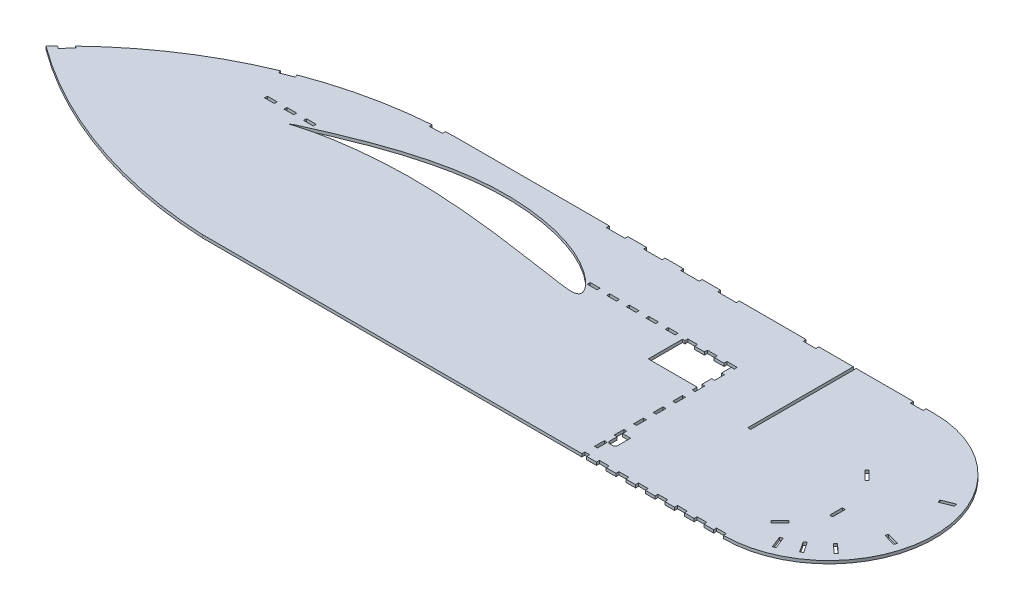
SolidWorks part; units mm, degrees
ref_plane "Front Plane" through (0, 0, 0) normal (0, 0, 1) x (1, 0, 0)
ref_plane "Top Plane" through (0, 0, 0) normal (0, 1, 0) x (1, 0, 0)
ref_plane "Right Plane" through (0, 0, 0) normal (1, 0, 0) x (0, 0, -1)
sketch "Sketch1" plane through (0, 0, 0) normal (0, 1, 0) x (1, 0, 0)
  line L0 (800, 108) -> (0, 108) construction
  line L1 (266.4083, 0) -> (800, 0)
  line L2 (0, 0) -> (0, 216) construction
  line L3 (316.2946, 216) -> (800, 216)
  arc A0 (800, 216) -> (800, 0) centre (800, 108) cw
  arc A2 (266.4083, 0) -> (19.4291, 86.8932) centre (286.1808, 450.645) cw
  arc A4 (19.4291, 86.8932) -> (316.2946, 216) centre (316.2946, -189.8565) cw
  dimension "D1" = 800
  dimension "D2" = 216
extrude "Boss-Extrude1" add sketch "Sketch1" along normal blind 3
sketch "Sketch2" plane through (0, 0, 0) normal (0, -1, 0) x (1, 0, 0)
  line L0 (605.07, -153) -> (605.07, 81) construction
  line L1 (647.57, -153) -> (637.57, -153)
  line L2 (655.07, -153) -> (655.07, -143)
  line L3 (655.07, -118) -> (605.07, -118)
  line L4 (823.6893, -121.2328) -> (814.4969, -130.4252)
  line L5 (814.4969, -130.4252) -> (816.6182, -132.5465)
  line L6 (816.6182, -132.5465) -> (825.8106, -123.3541)
  line L7 (825.8106, -123.3541) -> (823.6893, -121.2328)
  line L8 (823.6893, -121.2328) -> (814.4969, -130.4252)
  line L9 (814.4969, -130.4252) -> (816.6182, -132.5465)
  line L10 (816.6182, -132.5465) -> (825.8106, -123.3541)
  line L11 (825.8106, -123.3541) -> (823.6893, -121.2328)
  line L12 (605.07, -153) -> (605.07, -118)
  line L13 (778.5, -216) -> (791.5, -216) construction
  line L14 (791.5, -216) -> (791.5, -213) construction
  line L15 (791.5, -213) -> (778.5, -213) construction
  line L16 (778.5, -213) -> (778.5, -216) construction
  line L17 (668.6076, -216) -> (681.6076, -216) construction
  line L18 (681.6076, -216) -> (681.6076, -213) construction
  line L19 (681.6076, -213) -> (668.6076, -213) construction
  line L20 (833.1606, -28.1059) -> (837.9352, -16.0144)
  line L21 (837.9352, -16.0144) -> (835.1449, -14.9126)
  line L22 (835.1449, -14.9126) -> (830.3703, -27.0041)
  line L23 (830.3703, -27.0041) -> (833.1606, -28.1059)
  line L24 (833.1606, -28.1059) -> (837.9352, -16.0144)
  line L25 (837.9352, -16.0144) -> (835.1449, -14.9126)
  line L26 (835.1449, -14.9126) -> (830.3703, -27.0041)
  line L27 (830.3703, -27.0041) -> (833.1606, -28.1059)
  line L28 (839.4566, -85.3169) -> (839.4566, -72.3169)
  line L29 (839.4566, -72.3169) -> (836.4566, -72.3169)
  line L30 (836.4566, -72.3169) -> (836.4566, -85.3169)
  line L31 (836.4566, -85.3169) -> (839.4566, -85.3169)
  line L32 (839.4566, -85.3169) -> (839.4566, -72.3169)
  line L33 (839.4566, -72.3169) -> (836.4566, -72.3169)
  line L34 (836.4566, -72.3169) -> (836.4566, -85.3169)
  line L35 (836.4566, -85.3169) -> (839.4566, -85.3169)
  line L36 (668.6076, -213) -> (668.6076, -216) construction
  line L39 (600.2018, -213) -> (581.2018, -213) construction
  line L40 (658.07, -25.4734) -> (658.07, -38.6734)
  line L41 (663.77, -22.9734) -> (660.57, -22.9734)
  line L42 (666.27, -38.6734) -> (666.27, -25.4734)
  line L43 (658.07, -38.6734) -> (666.27, -38.6734)
  line L44 (658.07, -25.4734) -> (658.07, -33)
  line L45 (663.77, -22.9734) -> (660.57, -22.9734)
  line L46 (666.27, -38.6734) -> (666.27, -25.4734)
  line L47 (658.07, -38.6734) -> (666.27, -38.6734)
  line L48 (581.2018, -213) -> (581.2018, -216) construction
  line L49 (581.2018, -216) -> (600.2018, -216) construction
  line L50 (600.2018, -216) -> (600.2018, -213) construction
  line L51 (562.2018, -213) -> (543.2018, -213) construction
  line L52 (543.2018, -213) -> (543.2018, -216) construction
  line L53 (543.2018, -216) -> (562.2018, -216) construction
  line L54 (562.2018, -216) -> (562.2018, -213) construction
  line L55 (524.2018, -213) -> (505.2018, -213) construction
  line L56 (505.2018, -213) -> (505.2018, -216) construction
  line L57 (505.2018, -216) -> (524.2018, -216) construction
  line L58 (524.2018, -216) -> (524.2018, -213) construction
  line L59 (486.2018, -213) -> (467.2018, -213) construction
  line L60 (467.2018, -213) -> (467.2018, -216) construction
  line L61 (467.2018, -216) -> (486.2018, -216) construction
  line L62 (486.2018, -216) -> (486.2018, -213) construction
  line L63 (286.6536, -215.0679) -> (299.64, -215.6627) construction
  line L64 (299.64, -215.6627) -> (299.7772, -212.6658) construction
  line L65 (299.7772, -212.6658) -> (286.7909, -212.0711) construction
  line L66 (286.7909, -212.0711) -> (286.6536, -215.0679) construction
  line L67 (161.1801, -185.2358) -> (173.2648, -190.0276) construction
  line L68 (173.2648, -190.0276) -> (174.3706, -187.2388) construction
  line L69 (174.3706, -187.2388) -> (162.2859, -182.447) construction
  line L70 (162.2859, -182.447) -> (161.1801, -185.2358) construction
  line L71 (25.2251, -93.1105) -> (34.0897, -102.6194) construction
  line L72 (34.0897, -102.6194) -> (36.2841, -100.5738) construction
  line L73 (36.2841, -100.5738) -> (27.4195, -91.0649) construction
  line L74 (27.4195, -91.0649) -> (25.2251, -93.1105) construction
  line L75 (212.57, -142.2618) -> (212.57, -142.2948)
  line L131 (537.57, -153) -> (527.57, -153) construction
  line L132 (527.57, -153) -> (527.57, -156) construction
  line L133 (527.57, -156) -> (537.57, -156) construction
  line L134 (537.57, -156) -> (537.57, -153) construction
  line L135 (557.57, -153) -> (547.57, -153) construction
  line L136 (547.57, -153) -> (547.57, -156) construction
  line L137 (547.57, -156) -> (557.57, -156) construction
  line L138 (557.57, -156) -> (557.57, -153) construction
  line L139 (577.57, -153) -> (567.57, -153) construction
  line L140 (567.57, -153) -> (567.57, -156) construction
  line L141 (567.57, -156) -> (577.57, -156) construction
  line L142 (577.57, -156) -> (577.57, -153) construction
  line L143 (597.57, -153) -> (587.57, -153) construction
  line L144 (587.57, -153) -> (587.57, -156) construction
  line L145 (587.57, -156) -> (597.57, -156) construction
  line L146 (597.57, -156) -> (597.57, -153) construction
  line L148 (607.57, -153) -> (607.57, -156) construction
  line L149 (607.57, -156) -> (617.57, -156) construction
  line L150 (617.57, -156) -> (617.57, -153) construction
  line L152 (627.57, -153) -> (627.57, -156) construction
  line L153 (627.57, -156) -> (637.57, -156) construction
  line L154 (637.57, -156) -> (637.57, -153) construction
  line L155 (658.07, -153) -> (647.57, -153) construction
  line L156 (647.57, -153) -> (647.57, -156) construction
  line L157 (647.57, -156) -> (658.07, -156) construction
  line L158 (658.07, -156) -> (658.07, -153) construction
  line L160 (655.07, -143) -> (658.07, -143) construction
  line L161 (658.07, -143) -> (658.07, -133) construction
  line L162 (658.07, -133) -> (655.07, -133) construction
  line L163 (655.07, -113) -> (655.07, -123) construction
  line L164 (655.07, -123) -> (658.07, -123) construction
  line L165 (658.07, -123) -> (658.07, -113) construction
  line L166 (658.07, -113) -> (655.07, -113) construction
  line L167 (655.07, -93) -> (655.07, -103) construction
  line L168 (655.07, -103) -> (658.07, -103) construction
  line L169 (658.07, -103) -> (658.07, -93) construction
  line L170 (658.07, -93) -> (655.07, -93) construction
  line L171 (655.07, -73) -> (655.07, -83) construction
  line L172 (655.07, -83) -> (658.07, -83) construction
  line L173 (658.07, -83) -> (658.07, -73) construction
  line L174 (658.07, -73) -> (655.07, -73) construction
  line L175 (655.07, -53) -> (655.07, -63) construction
  line L176 (655.07, -63) -> (658.07, -63) construction
  line L177 (658.07, -63) -> (658.07, -53) construction
  line L178 (658.07, -53) -> (655.07, -53) construction
  line L179 (655.07, -33) -> (655.07, -43) construction
  line L180 (655.07, -43) -> (658.07, -43) construction
  line L182 (658.07, -33) -> (655.07, -33) construction
  line L183 (655.07, -13) -> (655.07, -23) construction
  line L184 (655.07, -23) -> (658.07, -23) construction
  line L185 (658.07, -23) -> (658.07, -13) construction
  line L186 (658.07, -13) -> (655.07, -13) construction
  line L187 (660, 0) -> (655.07, 0) construction
  line L188 (879.4887, -142.1211) -> (891.5217, -147.041) construction
  line L189 (891.5217, -147.041) -> (892.6571, -144.2642) construction
  line L190 (892.6571, -144.2642) -> (880.6241, -139.3442) construction
  line L191 (880.6241, -139.3442) -> (879.4887, -142.1211) construction
  line L192 (883.5475, -85.5833) -> (896.0431, -81.9972) construction
  line L193 (896.0431, -81.9972) -> (895.2156, -79.1136) construction
  line L194 (895.2156, -79.1136) -> (882.72, -82.6997) construction
  line L195 (882.72, -82.6997) -> (883.5475, -85.5833) construction
  line L196 (865.3607, -51.3372) -> (875.0343, -42.6526) construction
  line L197 (875.0343, -42.6526) -> (873.0302, -40.4202) construction
  line L198 (873.0302, -40.4202) -> (863.3566, -49.1048) construction
  line L199 (863.3566, -49.1048) -> (865.3607, -51.3372) construction
  line L200 (849.0648, -36.7585) -> (856.2517, -25.9258) construction
  line L201 (856.2517, -25.9258) -> (853.7518, -24.2673) construction
  line L202 (853.7518, -24.2673) -> (846.5649, -35.1) construction
  line L203 (846.5649, -35.1) -> (849.0648, -36.7585) construction
  line L204 (822.4089, -44.7346) -> (813.2165, -35.5422) construction
  line L205 (813.2165, -35.5422) -> (811.0952, -37.6635) construction
  line L206 (811.0952, -37.6635) -> (820.2876, -46.8559) construction
  line L207 (820.2876, -46.8559) -> (822.4089, -44.7346) construction
  line L208 (879.4887, -142.1211) -> (891.5217, -147.041)
  line L209 (891.5217, -147.041) -> (892.6571, -144.2642)
  line L210 (892.6571, -144.2642) -> (880.6241, -139.3442)
  line L211 (880.6241, -139.3442) -> (879.4887, -142.1211)
  line L212 (883.5475, -85.5833) -> (896.0431, -81.9972)
  line L213 (896.0431, -81.9972) -> (895.2156, -79.1136)
  line L214 (895.2156, -79.1136) -> (882.72, -82.6997)
  line L215 (882.72, -82.6997) -> (883.5475, -85.5833)
  line L216 (865.3607, -51.3372) -> (875.0343, -42.6526)
  line L217 (875.0343, -42.6526) -> (873.0302, -40.4202)
  line L218 (873.0302, -40.4202) -> (863.3566, -49.1048)
  line L219 (863.3566, -49.1048) -> (865.3607, -51.3372)
  line L220 (849.0648, -36.7585) -> (856.2517, -25.9258)
  line L221 (856.2517, -25.9258) -> (853.7518, -24.2673)
  line L222 (853.7518, -24.2673) -> (846.5649, -35.1)
  line L223 (846.5649, -35.1) -> (849.0648, -36.7585)
  line L224 (822.4089, -44.7346) -> (813.2165, -35.5422)
  line L225 (813.2165, -35.5422) -> (811.0952, -37.6635)
  line L226 (811.0952, -37.6635) -> (820.2876, -46.8559)
  line L227 (820.2876, -46.8559) -> (822.4089, -44.7346)
  line L228 (655.07, 0) -> (655.07, -3) construction
  line L229 (655.07, -3) -> (660, -3) construction
  line L230 (660, -3) -> (660, 0) construction
  line L231 (680, 0) -> (670, 0) construction
  line L232 (670, 0) -> (670, -3) construction
  line L233 (670, -3) -> (680, -3) construction
  line L234 (680, -3) -> (680, 0) construction
  line L235 (700, 0) -> (690, 0) construction
  line L236 (690, 0) -> (690, -3) construction
  line L237 (690, -3) -> (700, -3) construction
  line L238 (700, -3) -> (700, 0) construction
  line L239 (720, 0) -> (710, 0) construction
  line L240 (710, 0) -> (710, -3) construction
  line L241 (710, -3) -> (720, -3) construction
  line L242 (720, -3) -> (720, 0) construction
  line L243 (740, 0) -> (730, 0) construction
  line L244 (730, 0) -> (730, -3) construction
  line L245 (730, -3) -> (740, -3) construction
  line L246 (740, -3) -> (740, 0) construction
  line L247 (760, 0) -> (750, 0) construction
  line L248 (750, 0) -> (750, -3) construction
  line L249 (750, -3) -> (760, -3) construction
  line L250 (760, -3) -> (760, 0) construction
  line L251 (780, 0) -> (770, 0) construction
  line L252 (770, 0) -> (770, -3) construction
  line L253 (770, -3) -> (780, -3) construction
  line L254 (780, -3) -> (780, 0) construction
  line L255 (800, 0) -> (790, 0) construction
  line L256 (790, 0) -> (790, -3) construction
  line L257 (790, -3) -> (800, -3) construction
  line L258 (800, -3) -> (800, 0) construction
  line L259 (778.5, -216) -> (791.5, -216)
  line L260 (791.5, -216) -> (791.5, -213)
  line L261 (791.5, -213) -> (778.5, -213)
  line L262 (778.5, -213) -> (778.5, -216)
  line L263 (668.6076, -216) -> (681.6076, -216)
  line L264 (681.6076, -216) -> (681.6076, -213)
  line L265 (681.6076, -213) -> (668.6076, -213)
  line L266 (668.6076, -213) -> (668.6076, -216)
  line L267 (600.2018, -213) -> (581.2018, -213)
  line L268 (581.2018, -213) -> (581.2018, -216)
  line L269 (581.2018, -216) -> (600.2018, -216)
  line L270 (600.2018, -216) -> (600.2018, -213)
  line L271 (562.2018, -213) -> (543.2018, -213)
  line L272 (543.2018, -213) -> (543.2018, -216)
  line L273 (543.2018, -216) -> (562.2018, -216)
  line L274 (562.2018, -216) -> (562.2018, -213)
  line L275 (524.2018, -213) -> (505.2018, -213)
  line L276 (505.2018, -213) -> (505.2018, -216)
  line L277 (505.2018, -216) -> (524.2018, -216)
  line L278 (524.2018, -216) -> (524.2018, -213)
  line L279 (486.2018, -213) -> (467.2018, -213)
  line L280 (467.2018, -213) -> (467.2018, -216)
  line L281 (467.2018, -216) -> (486.2018, -216)
  line L282 (486.2018, -216) -> (486.2018, -213)
  line L283 (286.6536, -215.0679) -> (299.64, -215.6627)
  line L284 (299.64, -215.6627) -> (299.7772, -212.6658)
  line L285 (299.7772, -212.6658) -> (286.7909, -212.0711)
  line L286 (286.7909, -212.0711) -> (286.6536, -215.0679)
  line L287 (161.1801, -185.2358) -> (173.2648, -190.0276)
  line L288 (173.2648, -190.0276) -> (174.3706, -187.2388)
  line L289 (174.3706, -187.2388) -> (162.2859, -182.447)
  line L290 (162.2859, -182.447) -> (161.1801, -185.2358)
  line L291 (25.2251, -93.1105) -> (34.0897, -102.6194)
  line L292 (34.0897, -102.6194) -> (36.2841, -100.5738)
  line L293 (36.2841, -100.5738) -> (27.4195, -91.0649)
  line L294 (27.4195, -91.0649) -> (25.2251, -93.1105)
  line L351 (537.57, -153) -> (527.57, -153)
  line L352 (527.57, -153) -> (527.57, -156)
  line L353 (527.57, -156) -> (537.57, -156)
  line L354 (537.57, -156) -> (537.57, -153)
  line L355 (557.57, -153) -> (547.57, -153)
  line L356 (547.57, -153) -> (547.57, -156)
  line L357 (547.57, -156) -> (557.57, -156)
  line L358 (557.57, -156) -> (557.57, -153)
  line L359 (577.57, -153) -> (567.57, -153)
  line L360 (567.57, -153) -> (567.57, -156)
  line L361 (567.57, -156) -> (577.57, -156)
  line L362 (577.57, -156) -> (577.57, -153)
  line L363 (597.57, -153) -> (587.57, -153)
  line L364 (587.57, -153) -> (587.57, -156)
  line L365 (587.57, -156) -> (597.57, -156)
  line L366 (597.57, -156) -> (597.57, -153)
  line L368 (607.57, -153) -> (607.57, -156)
  line L369 (607.57, -156) -> (617.57, -156)
  line L370 (617.57, -156) -> (617.57, -153)
  line L372 (627.57, -153) -> (627.57, -156)
  line L373 (627.57, -156) -> (637.57, -156)
  line L374 (637.57, -156) -> (637.57, -153)
  line L375 (658.07, -153) -> (655.07, -153)
  line L376 (647.57, -153) -> (647.57, -156)
  line L377 (647.57, -156) -> (658.07, -156)
  line L378 (658.07, -156) -> (658.07, -153)
  line L380 (655.07, -143) -> (658.07, -143)
  line L381 (658.07, -143) -> (658.07, -133)
  line L382 (658.07, -133) -> (655.07, -133)
  line L383 (655.07, -113) -> (655.07, -118)
  line L384 (655.07, -123) -> (658.07, -123)
  line L385 (658.07, -123) -> (658.07, -113)
  line L386 (658.07, -113) -> (655.07, -113)
  line L387 (655.07, -93) -> (655.07, -103)
  line L388 (655.07, -103) -> (658.07, -103)
  line L389 (658.07, -103) -> (658.07, -93)
  line L390 (658.07, -93) -> (655.07, -93)
  line L391 (655.07, -73) -> (655.07, -83)
  line L392 (655.07, -83) -> (658.07, -83)
  line L393 (658.07, -83) -> (658.07, -73)
  line L394 (658.07, -73) -> (655.07, -73)
  line L395 (655.07, -53) -> (655.07, -63)
  line L396 (655.07, -63) -> (658.07, -63)
  line L397 (658.07, -63) -> (658.07, -53)
  line L398 (658.07, -53) -> (655.07, -53)
  line L399 (655.07, -33) -> (655.07, -43)
  line L400 (655.07, -43) -> (658.07, -43)
  line L401 (658.07, -43) -> (658.07, -38.6734)
  line L402 (658.07, -33) -> (655.07, -33)
  line L403 (655.07, -13) -> (655.07, -23)
  line L404 (655.07, -23) -> (658.07, -23)
  line L405 (658.07, -23) -> (658.07, -13)
  line L406 (658.07, -13) -> (655.07, -13)
  line L407 (660, 0) -> (655.07, 0)
  line L408 (655.07, 0) -> (655.07, -3)
  line L409 (655.07, -3) -> (660, -3)
  line L410 (660, -3) -> (660, 0)
  line L411 (680, 0) -> (670, 0)
  line L412 (670, 0) -> (670, -3)
  line L413 (670, -3) -> (680, -3)
  line L414 (680, -3) -> (680, 0)
  line L415 (700, 0) -> (690, 0)
  line L416 (690, 0) -> (690, -3)
  line L417 (690, -3) -> (700, -3)
  line L418 (700, -3) -> (700, 0)
  line L419 (720, 0) -> (710, 0)
  line L420 (710, 0) -> (710, -3)
  line L421 (710, -3) -> (720, -3)
  line L422 (720, -3) -> (720, 0)
  line L423 (740, 0) -> (730, 0)
  line L424 (730, 0) -> (730, -3)
  line L425 (730, -3) -> (740, -3)
  line L426 (740, -3) -> (740, 0)
  line L427 (760, 0) -> (750, 0)
  line L428 (750, 0) -> (750, -3)
  line L429 (750, -3) -> (760, -3)
  line L430 (760, -3) -> (760, 0)
  line L431 (780, 0) -> (770, 0)
  line L432 (770, 0) -> (770, -3)
  line L433 (770, -3) -> (780, -3)
  line L434 (780, -3) -> (780, 0)
  line L435 (800, 0) -> (790, 0)
  line L436 (790, 0) -> (790, -3)
  line L437 (790, -3) -> (800, -3)
  line L438 (800, -3) -> (800, 0)
  line L439 (655.07, -133) -> (655.07, -123)
  line L440 (627.57, -153) -> (617.57, -153)
  line L441 (607.57, -153) -> (605.07, -153)
  line L462 (187.07, -153) -> (177.07, -153) construction
  line L463 (177.07, -153) -> (177.07, -156) construction
  line L464 (177.07, -156) -> (187.07, -156) construction
  line L465 (187.07, -156) -> (187.07, -153) construction
  line L466 (207.07, -153) -> (197.07, -153) construction
  line L467 (197.07, -153) -> (197.07, -156) construction
  line L468 (197.07, -156) -> (207.07, -156) construction
  line L469 (207.07, -156) -> (207.07, -153) construction
  line L470 (227.07, -153) -> (217.07, -153) construction
  line L471 (217.07, -153) -> (217.07, -156) construction
  line L472 (217.07, -156) -> (227.07, -156) construction
  line L473 (227.07, -156) -> (227.07, -153) construction
  line L474 (517.57, -153) -> (507.57, -153) construction
  line L475 (507.57, -153) -> (507.57, -156) construction
  line L476 (507.57, -156) -> (517.57, -156) construction
  line L477 (517.57, -156) -> (517.57, -153) construction
  line L478 (187.07, -153) -> (177.07, -153)
  line L479 (177.07, -153) -> (177.07, -156)
  line L480 (177.07, -156) -> (187.07, -156)
  line L481 (187.07, -156) -> (187.07, -153)
  line L482 (207.07, -153) -> (197.07, -153)
  line L483 (197.07, -153) -> (197.07, -156)
  line L484 (197.07, -156) -> (207.07, -156)
  line L485 (207.07, -156) -> (207.07, -153)
  line L486 (227.07, -153) -> (217.07, -153)
  line L487 (217.07, -153) -> (217.07, -156)
  line L488 (217.07, -156) -> (227.07, -156)
  line L489 (227.07, -156) -> (227.07, -153)
  line L490 (517.57, -153) -> (507.57, -153)
  line L491 (507.57, -153) -> (507.57, -156)
  line L492 (507.57, -156) -> (517.57, -156)
  line L493 (517.57, -156) -> (517.57, -153)
  line L534 (717, -108) -> (717, -216)
  line L535 (717, -216) -> (720, -216)
  line L536 (720, -216) -> (720, -108)
  line L537 (720, -108) -> (717, -108)
  line L538 (717, -108) -> (717, -216)
  line L539 (717, -216) -> (720, -216)
  line L540 (720, -216) -> (720, -108)
  line L541 (720, -108) -> (717, -108)
  arc A2 (660.57, -22.9734) -> (658.07, -25.4734) centre (660.57, -25.4734) ccw
  arc A3 (666.27, -25.4734) -> (663.77, -22.9734) centre (663.77, -25.4734) ccw
  arc A4 (660.57, -22.9734) -> (658.07, -25.4734) centre (660.57, -25.4734) ccw
  arc A5 (666.27, -25.4734) -> (663.77, -22.9734) centre (663.77, -25.4734) ccw
  spline S0 degree 3 poles (-1490.7318, -2610.4866) (189.7857, -84.8289) (191.8397, -130.1262) (215.6642, -144.2206) (218.7234, -145.7779) (222.7838, -147.5804) (227.7591, -149.7808) (233.6732, -152.3729) (243.3346, -156.474) (254.0716, -160.9286) (265.8113, -165.5514) (275.5598, -169.1926) (285.8203, -172.7897) (300.2132, -177.4429) (315.0475, -181.6144) (330.2168, -185.0782) (341.7168, -187.2628) (353.2384, -188.9705) (364.7498, -190.1898) (376.2222, -190.8893) (387.6115, -191.0869) (398.8538, -190.7647) (413.4214, -189.6963) (427.5808, -187.7) (441.1954, -184.8275) (450.8219, -182.3197) (459.9489, -179.4697) (468.5117, -176.2876) (476.4536, -172.8247) (483.7151, -169.1289) (490.2481, -165.2848) (496.0197, -161.4069) (500.998, -157.5857) (505.1476, -153.8841) (508.4473, -150.3827) (510.8522, -147.1808) (512.2305, -144.519) (512.6724, -142.438) (512.366, -140.694) (510.8363, -139.2679) (508.3008, -138.6046) (504.9907, -138.3969) (500.8451, -138.6329) (495.8864, -139.207) (490.1274, -140.0338) (483.6007, -141.0142) (476.346, -142.082) (468.4189, -143.2709) (459.8696, -144.553) (447.4042, -146.414) (434.3028, -148.292) (413.2306, -151.0803) (394.9165, -153.1705) (372.4131, -155.1852) (353.2786, -156.4974) (334.1039, -157.1205) (318.8375, -157.1193) (307.5693, -156.8631) (296.5448, -156.3424) (285.8536, -155.5986) (275.5863, -154.6546) (265.8296, -153.5569) (256.6735, -152.3128) (248.205, -150.9585) (240.5101, -149.5233) (233.6661, -148.0641) (227.7356, -146.6296) (222.7715, -145.2056) (218.7746, -143.9126) (215.7248, -142.9952) (190.4211, -136.5967) (159.0994, -163.5562) (767.7445, 2804.8334) knots -0.121434 -0.121434 -0.121434 -0.121434 0.001413 0.005226 0.010781 0.017816 0.026461 0.036791 0.048686 0.076639 0.092363 0.109003 0.126387 0.144339 0.181313 0.200023 0.218713 0.237261 0.255692 0.274037 0.292193 0.310133 0.327788 0.362002 0.378421 0.394287 0.409543 0.424114 0.437938 0.450942 0.463044 0.474154 0.484165 0.493024 0.500713 0.507126 0.51213 0.514904 0.517171 0.520262 0.524245 0.529498 0.536092 0.544061 0.553363 0.563905 0.575615 0.58842 0.602227 0.616944 0.648676 0.665501 0.718564 0.736789 0.773513 0.810245 0.828489 0.846493 0.864125 0.881249 0.897725 0.913415 0.928184 0.941897 0.954411 0.965603 0.97535 0.983576 0.990285 0.995433 0.9988 1.114983 1.114983 1.114983 1.114983 only from (212.57, -142.2948) to (212.57, -142.2618) construction
  spline S1 degree 3 poles (212.57, -142.2948) (212.8151, -142.4601) (213.7215, -143.0713) (215.6642, -144.2206) (218.7234, -145.7779) (222.7838, -147.5804) (227.7591, -149.7808) (233.6732, -152.3729) (243.3346, -156.474) (254.0716, -160.9286) (265.8113, -165.5514) (275.5598, -169.1926) (285.8203, -172.7897) (300.2132, -177.4429) (315.0475, -181.6144) (330.2168, -185.0782) (341.7168, -187.2628) (353.2384, -188.9705) (364.7498, -190.1898) (376.2222, -190.8893) (387.6115, -191.0869) (398.8538, -190.7647) (413.4214, -189.6963) (427.5808, -187.7) (441.1954, -184.8275) (450.8219, -182.3197) (459.9489, -179.4697) (468.5117, -176.2876) (476.4536, -172.8247) (483.7151, -169.1289) (490.2481, -165.2848) (496.0197, -161.4069) (500.998, -157.5857) (505.1476, -153.8841) (508.4473, -150.3827) (510.8522, -147.1808) (512.2305, -144.519) (512.6724, -142.438) (512.366, -140.694) (510.8363, -139.2679) (508.3008, -138.6046) (504.9907, -138.3969) (500.8451, -138.6329) (495.8864, -139.207) (490.1274, -140.0338) (483.6007, -141.0142) (476.346, -142.082) (468.4189, -143.2709) (459.8696, -144.553) (447.4042, -146.414) (434.3028, -148.292) (413.2306, -151.0803) (394.9165, -153.1705) (372.4131, -155.1852) (353.2786, -156.4974) (334.1039, -157.1205) (318.8375, -157.1193) (307.5693, -156.8631) (296.5448, -156.3424) (285.8536, -155.5986) (275.5863, -154.6546) (265.8296, -153.5569) (256.6735, -152.3128) (248.205, -150.9585) (240.5101, -149.5233) (233.6661, -148.0641) (227.7356, -146.6296) (222.7715, -145.2056) (218.7746, -143.9126) (215.7248, -142.9952) (213.7534, -142.4967) (212.8162, -142.3107) (212.57, -142.2618) knots 0 0 0 0 0.001413 0.005226 0.010781 0.017816 0.026461 0.036791 0.048686 0.076639 0.092363 0.109003 0.126387 0.144339 0.181313 0.200023 0.218713 0.237261 0.255692 0.274037 0.292193 0.310133 0.327788 0.362002 0.378421 0.394287 0.409543 0.424114 0.437938 0.450942 0.463044 0.474154 0.484165 0.493024 0.500713 0.507126 0.51213 0.514904 0.517171 0.520262 0.524245 0.529498 0.536092 0.544061 0.553363 0.563905 0.575615 0.58842 0.602227 0.616944 0.648676 0.665501 0.718564 0.736789 0.773513 0.810245 0.828489 0.846493 0.864125 0.881249 0.897725 0.913415 0.928184 0.941897 0.954411 0.965603 0.97535 0.983576 0.990285 0.995433 0.9988 1 1 1 1
  dimension "D6" = 35
  dimension "D1" = 0
  dimension "D2" = 0
  dimension "D3" = 0
  dimension "D4" = 0
  dimension "D5" = 0
extrude "Cut-Extrude1" cut sketch "Sketch2" against normal through all
